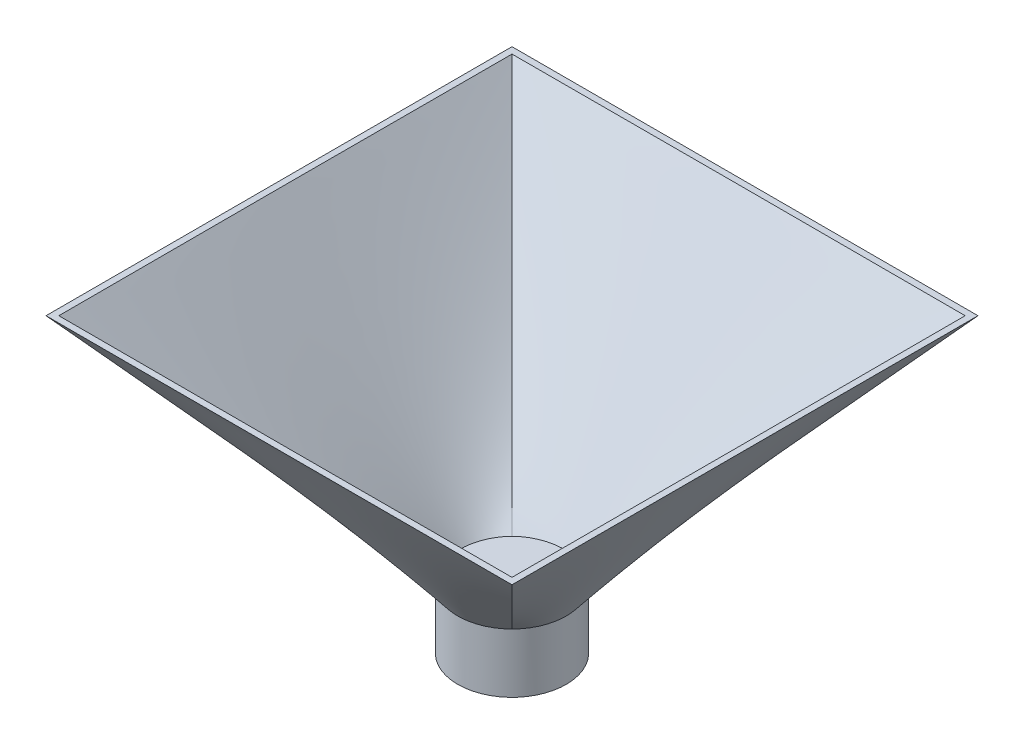
SolidWorks part; units mm, degrees
ref_plane "Front" through (0, 0, 0) normal (0, 0, 1) x (1, 0, 0)
ref_plane "Top" through (0, 0, 0) normal (0, 1, 0) x (1, 0, 0)
ref_plane "Right" through (0, 0, 0) normal (1, 0, 0) x (0, 0, -1)
sketch "Croquis1" plane through (0, 0, 0) normal (0, 1, 0) x (1, 0, 0)
  circle A0 centre (0, 0) radius 63.5
  circle A1 centre (0, 0) radius 69.85
  dimension "D1" = 127
  dimension "D2" = 6.35
extrude "Saliente-Extruir1" add sketch "Croquis1" along normal blind 76.2
sketch "Croquis2" plane through (0, 76.2, 0) normal (0, 1, 0) x (1, 0, 0)
  circle A0 centre (0, 0) radius 69.85
ref_plane "Plano1" through (0, 376.2, 0) normal (0, 1, 0) x (1, 0, 0)
sketch "Croquis4" plane through (0, 376.2, 0) normal (0, 1, 0) x (1, 0, 0)
  line L1 (-300, 300) -> (300, 300)
  line L2 (-300, 300) -> (-300, -300)
  line L3 (-300, -300) -> (300, -300)
  line L4 (300, 300) -> (300, -300)
  line L5 (-300, 300) -> (300, -300) construction
  line L6 (-300, -300) -> (300, 300) construction
  point P0 (0, 0)
  dimension "D1" = 600
  dimension "D2" = 600
loft "Recubrir1" add profiles "Croquis4", "Croquis2" connector at (-300, 376.2, 300) connector at (5.6116, 76.2, 69.6242)
shell "Vaciado1" thickness 6.35 removed face at (0, 376.2, 0)
